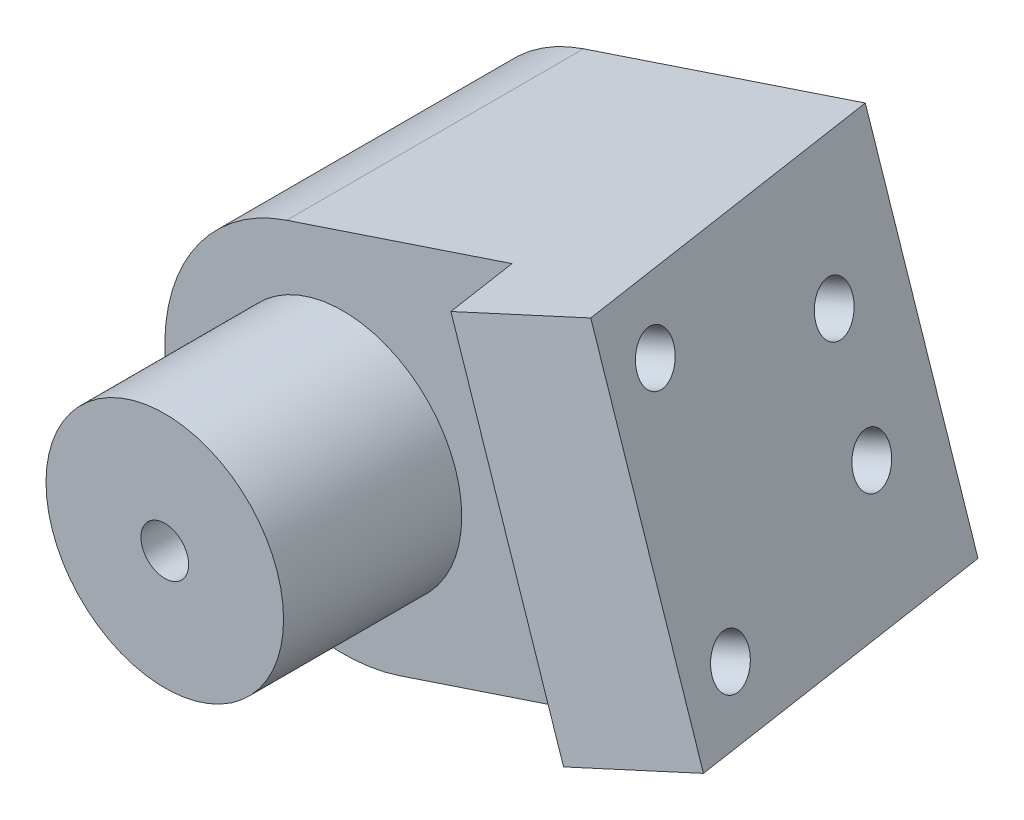
SolidWorks part; units mm, degrees
material "6061 Alloy"
ref_plane "Front Plane" through (0, 0, 0) normal (0, 0, 1) x (1, 0, 0)
ref_plane "Top Plane" through (0, 0, 0) normal (0, 1, 0) x (1, 0, 0)
ref_plane "Right Plane" through (0, 0, 0) normal (1, 0, 0) x (0, 0, -1)
sketch "Sketch1" plane through (0, 0, 0) normal (0, 0, 1) x (1, 0, 0)
  line L0 (0, 0) -> (228.6, 76.2) construction
  line L1 (18.0724, 26.1046) -> (30.1207, -10.0402)
  line L2 (18.0724, 26.1046) -> (-6.0241, 18.0724)
  line L3 (30.1207, -10.0402) -> (6.0241, -18.0724)
  arc A0 (-6.0241, 18.0724) -> (6.0241, -18.0724) centre (0, 0) ccw
  point P6 (24.0966, 8.0322)
  dimension "D1" = 38.1
  dimension "D2" = 76.2
  dimension "D3" = 228.6
  dimension "D4" = 25.4
  dimension "D5" = 38.1
extrude "Boss-Extrude1" add sketch "Sketch1" along normal blind 31.75
sketch "Sketch10" plane through (-6.0241, 18.0724, 0) normal (-0.3162, 0.9487, 0) x (0.9487, 0.3162, 0)
  line L0 (25.4, 0) -> (31.75, 0)
  line L1 (31.75, 0) -> (40.0151, -37.1927)
  line L2 (40.0151, -37.1927) -> (27.2403, -40.0316)
  line L3 (27.2403, -40.0316) -> (25.4, -31.75)
  line L4 (25.4, -31.75) -> (25.4, 0) construction
  line L5 (25.4, 0) -> (25.4, -31.75)
  dimension "D1" = 38.1
  dimension "D2" = 6.35
  dimension "D3" = 12.529
extrude "Boss-Extrude4" add sketch "Sketch10" against normal blind 38.1 contours L1 L2 L3 L5 L0
sketch "Sketch11" plane through (0, 0, 31.75) normal (0, 0, 1) x (1, 0, 0)
  circle A0 centre (0, 0) radius 12.7
  dimension "D1" = 25.4
extrude "Boss-Extrude5" add sketch "Sketch11" along normal blind 19.05
hole_wizard "1/4-20 Tapped Hole3" positions "Sketch13" profile "Sketch12" tap size "1/4-20" standard "ANSI Inch"
sketch "Sketch13" plane through (0, 0, 50.8) normal (0, 0, 1) x (1, 0, 0)
  point P0 (0, 0)
sketch "Sketch12" plane through (0, 0, 50.8) normal (1, 0, 0) x (0, -1, 0)
  line L0 (0, 0) -> (0, 39.6338)
  line L1 (0, 39.6338) -> (2.5527, 38.1)
  line L2 (2.5527, 38.1) -> (2.5527, 0)
  line L5 (2.5527, 0) -> (0, 0)
  line L10 (0, 39.6338) -> (-2.5527, 38.1) construction
  line L11 (0, -6.35) -> (0, 107.95) construction
  dimension "Tap Drill Dia." = 5.1054
  dimension "Tap Drill Depth" = 38.1
  dimension "Drill Angle" = 118
cosmetic thread "Hole Thread9"
hole_wizard "1/4-20 Tapped Hole4" positions "Sketch15" profile "Sketch14" tap size "1/4-20" standard "ANSI Inch"
sketch "Sketch15" plane through (28.7033, 9.5678, -6.7235) normal (0.9261, 0.3087, -0.2169) x (-0.2058, -0.0686, -0.9762)
  line L0 (-44.9875, -19.05) -> (-44.9875, 19.05) construction
  line L1 (-6.8875, 19.05) -> (-44.9875, 19.05) construction
  line L2 (-6.8875, -19.05) -> (-44.9875, -19.05) construction
  line L3 (-6.8875, -19.05) -> (-6.8875, 19.05) construction
  point P0 (-38.6375, 12.7)
  point P2 (-16.4125, 6.35)
  point P4 (-16.4125, -6.35)
  point P6 (-38.6375, -12.7)
  dimension "D1" = 6.35
  dimension "D2" = 6.35
  dimension "D3" = 6.35
  dimension "D4" = 12.7
  dimension "D5" = 12.7
  dimension "D6" = 9.525
sketch "Sketch14" plane through (32.6387, 24.2665, 30.9939) normal (-0.0699, 0.7054, 0.7054) x (-0.3708, 0.6381, -0.6748)
  line L0 (0, 0) -> (0, 12.9638)
  line L1 (0, 12.9638) -> (2.5527, 11.43)
  line L2 (2.5527, 11.43) -> (2.5527, 0)
  line L5 (2.5527, 0) -> (0, 0)
  line L10 (0, 12.9638) -> (-2.5527, 11.43) construction
  line L11 (0, -6.35) -> (0, 107.95) construction
  dimension "Tap Drill Dia." = 5.1054
  dimension "Tap Drill Depth" = 11.43
  dimension "Drill Angle" = 118
cosmetic thread "Hole Thread10"
cosmetic thread "Hole Thread11"
cosmetic thread "Hole Thread12"
cosmetic thread "Hole Thread13"
sketch "Sketch16" plane through (0, 0, 0) normal (0, 0, -1) x (-1, 0, 0)
  line L0 (0, 0) -> (-27.1086, 9.0362) construction
  line L1 (-30.5782, -6.541) -> (-16.9994, -3.995)
  line L2 (-31.8416, -5.1627) -> (-17.2919, -2.4347)
  line L4 (-22.0885, 24.0966) -> (0, 0) construction
  line L5 (0, 0) -> (-32.1287, -6.0241) construction
  line L6 (-22.3756, 23.2351) -> (-12.3728, 12.3229)
  line L7 (5.0201, 15.0603) -> (-22.0885, 24.0966)
  line L8 (-22.0885, 24.0966) -> (-32.1287, -6.0241)
  line L9 (-32.1287, -6.0241) -> (-5.0201, -15.0603)
  line L10 (-1.8814, 17.3609) -> (-20.538, 23.5797)
  line L11 (-22.3756, 23.2351) -> (-31.8416, -5.1627)
  line L12 (-30.5782, -6.541) -> (-11.9216, -12.7598)
  line L13 (-20.538, 23.5797) -> (-11.2025, 13.3956)
  line L14 (-14.6146, 17.1178) -> (-15.7848, 16.0451) construction
  arc A0 (-16.9994, -3.995) -> (-11.9216, -12.7598) centre (0, 0) ccw
  arc A1 (-12.3728, 12.3229) -> (-17.2919, -2.4347) centre (0, 0) ccw
  arc A3 (-5.0201, -15.0603) -> (5.0201, 15.0603) centre (0, 0) ccw
  arc A5 (-1.8814, 17.3609) -> (-11.2025, 13.3956) centre (0, 0) ccw
  point P14 (-15.1997, 16.5815)
  dimension "D2" = 17.4625
  dimension "D3" = 1.5875
  dimension "D1" = 3.175
extrude "Cut-Extrude3" cut sketch "Sketch16" against normal blind 3.175
sketch "Sketch17" plane through (0, 0, 0) normal (0, 0, -1) x (-1, 0, 0)
  circle A0 centre (0, 0) radius 15.875
  dimension "D1" = 31.75
extrude "Cut-Extrude4" cut sketch "Sketch17" against normal blind 15.875
fillet "Fillet3" radius 1.5875 10 edges at (1.8814, 17.3609, 1.5875) (11.2025, 13.3956, 1.5875) (20.538, 23.5797, 1.5875) (22.3756, 23.2351, 1.5875) (12.3728, 12.3229, 1.5875) (17.2919, -2.4347, 1.5875) (16.9994, -3.995, 1.5875) (11.9216, -12.7598, 1.5875) (31.8416, -5.1627, 1.5875) (30.5782, -6.541, 1.5875)
ref_axis "Axis1" through (0, 0, 15.875) along (0, 0, 1)
sketch "Sketch18" plane through (28.7033, 9.5678, -6.7235) normal (0.9261, 0.3087, -0.2169) x (-0.2058, -0.0686, -0.9762)
  line L0 (-6.8875, 19.05) -> (-44.9875, -19.05) construction
  line L1 (-44.9875, -19.05) -> (-44.9875, 19.05) construction
  line L2 (-6.8875, -19.05) -> (-44.9875, 19.05) construction
  point P9 (-25.9375, 0)
sketch "Sketch19" plane through (0, 0, 15.875) normal (0, 0, -1) x (-1, 0, 0)
  line L0 (0, 0) -> (0, 15.875) construction
  line L1 (1.5875, 4.4901) -> (1.5875, 15.7954)
  line L2 (-1.5875, 4.4901) -> (-1.5875, 15.7954)
  line L3 (-1.5875, 10.1428) -> (1.5875, 10.1428) construction
  line L4 (3.7798, 2.8973) -> (14.5318, 6.3909)
  line L5 (4.7609, -0.1223) -> (15.5129, 3.3713)
  line L6 (3.9235, -2.6995) -> (10.5686, -11.8457)
  line L7 (1.3549, -4.5657) -> (8, -13.7119)
  line L8 (-1.3549, -4.5657) -> (-8, -13.7119)
  line L9 (-3.9235, -2.6995) -> (-10.5686, -11.8457)
  line L10 (-4.7609, -0.1223) -> (-15.5129, 3.3713)
  line L11 (-3.7798, 2.8973) -> (-14.5318, 6.3909)
  arc A0 (-1.5875, 4.4901) -> (-3.7798, 2.8973) centre (0, 0) ccw
  circle A1 centre (0, 0) radius 15.875 construction
  circle A2 centre (0, 0) radius 15.875 construction
  circle A3 centre (0, 0) radius 3.175 construction
  arc A4 (-4.7609, -0.1223) -> (-3.9235, -2.6995) centre (0, 0) ccw
  arc A5 (3.7798, 2.8973) -> (1.5875, 4.4901) centre (0, 0) ccw
  arc A6 (3.9235, -2.6995) -> (4.7609, -0.1223) centre (0, 0) ccw
  arc A7 (-1.3549, -4.5657) -> (1.3549, -4.5657) centre (0, 0) ccw
  arc A8 (-15.5129, 3.3713) -> (-10.5686, -11.8457) centre (0, 0) ccw
  arc A9 (-1.5875, 15.7954) -> (-14.5318, 6.3909) centre (0, 0) ccw
  arc A10 (14.5318, 6.3909) -> (1.5875, 15.7954) centre (0, 0) ccw
  arc A11 (10.5686, -11.8457) -> (15.5129, 3.3713) centre (0, 0) ccw
  arc A12 (-8, -13.7119) -> (8, -13.7119) centre (0, 0) ccw
  point P14 (0, 10.1428)
  point P34 (0, 0)
  dimension "D2" = 1.5875
  dimension "D3" = 6.35
  dimension "D4" = 5
  dimension "D1" = 3.175
extrude "Cut-Extrude5" cut sketch "Sketch19" against normal blind 6.35
fillet "Fillet4" radius 1.5875 20 edges at (-1.5875, 4.4901, 19.05) (-3.7798, 2.8973, 19.05) (-14.5318, 6.3909, 19.05) (-1.5875, 15.7954, 19.05) (-10.5686, -11.8457, 19.05) (-15.5129, 3.3713, 19.05) (-3.9235, -2.6995, 19.05) (-4.7609, -0.1223, 19.05) (1.3549, -4.5657, 19.05) (-1.3549, -4.5657, 19.05) (-8, -13.7119, 19.05) (8, -13.7119, 19.05) (10.5686, -11.8457, 19.05) (3.9235, -2.6995, 19.05) (4.7609, -0.1223, 19.05) (15.5129, 3.3713, 19.05) (14.5318, 6.3909, 19.05) (1.5875, 15.7954, 19.05) (1.5875, 4.4901, 19.05) (3.7798, 2.8973, 19.05)
